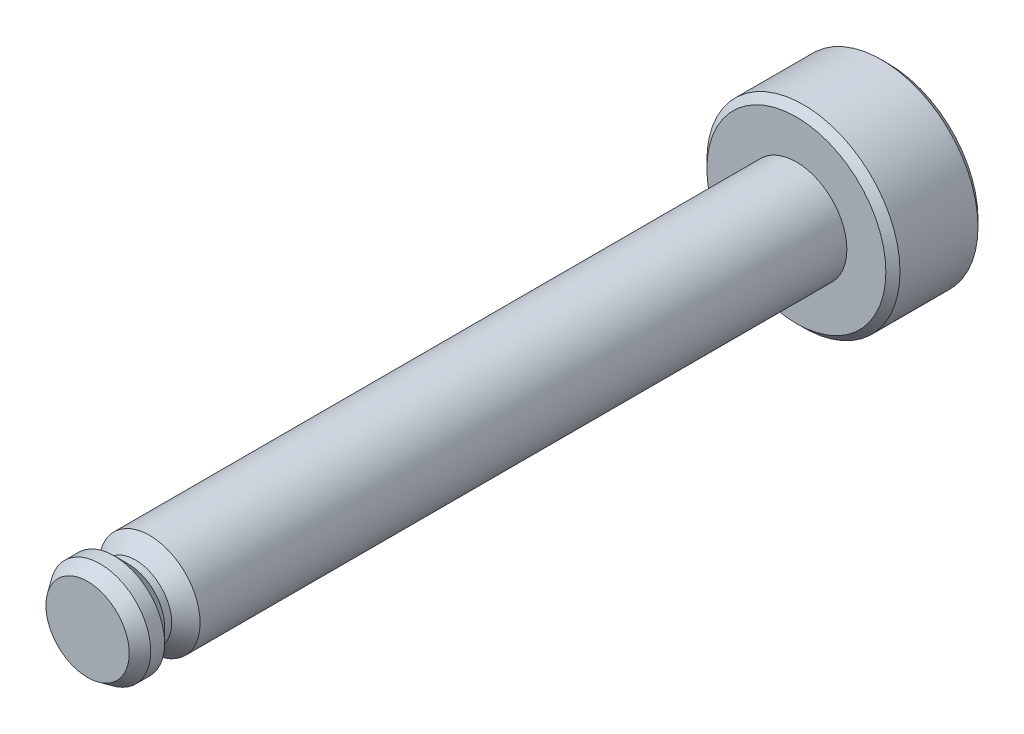
SolidWorks part; units mm, degrees
ref_plane "Front" through (0, 0, 0) normal (0, 0, 1) x (1, 0, 0)
ref_plane "Top" through (0, 0, 0) normal (0, 1, 0) x (1, 0, 0)
ref_plane "Right" through (0, 0, 0) normal (1, 0, 0) x (0, 0, -1)
sketch "Sketch2" plane through (0, 0, 0) normal (0, 0, 1) x (1, 0, 0)
  circle A0 centre (0, 0) radius 1.425
  dimension "D1" = 2.85
extrude "Shaft" add sketch "Sketch2" along normal blind 20
sketch "Sketch5" plane through (0, 0, 0) normal (0, 0, 1) x (1, 0, 0)
  circle A0 centre (0, 0) radius 2.725
  dimension "D1" = 5.45
extrude "Head" add sketch "Sketch5" against normal blind 2.6
sketch "Sketch4" plane through (0, 0, 0) normal (1, 0, 0) x (0, 0, -1)
  line L0 (0, 0) -> (-18.75, 0) construction
  line L1 (-18.75, 0) -> (-18.75, 4.3666) construction
  line L2 (-19.25, 1.425) -> (-18.25, 1.425)
  line L3 (0, 1.425) -> (-20, 1.425) construction
  line L6 (-18.25, 1.425) -> (-18.65, 1.025)
  line L7 (-18.65, 1.025) -> (-18.85, 1.025)
  line L8 (-18.85, 1.025) -> (-19.25, 1.425)
  dimension "D1" = 18.75
  dimension "D2" = 1
  dimension "D3" = 45
  dimension "D4" = 0.4
revolve "e-Clip Notch" cut sketch "Sketch4" angle 360 about L0
chamfer "Chamfer1" distance 0.25 angle 55 1 edges at (1.425, 0, 20) first distance on face at (1.425, 0, 20)
chamfer "Deburs" distance 0.2 angle 45 2 edges at (2.725, 0, 0) (2.725, 0, -2.6)
equation "\"D1@Sketch2\"=\"Hardware Clearance Hole Diameter@Box Assy.Assembly\"-.3"
equation "\"D1@Sketch5\"=\"Hardware Head Countersink Diameter@Box Assy.Assembly\"-.3mm"
equation "\"D1@Head\"=\"Nut Trap Depth@Box Assy.Assembly\""
